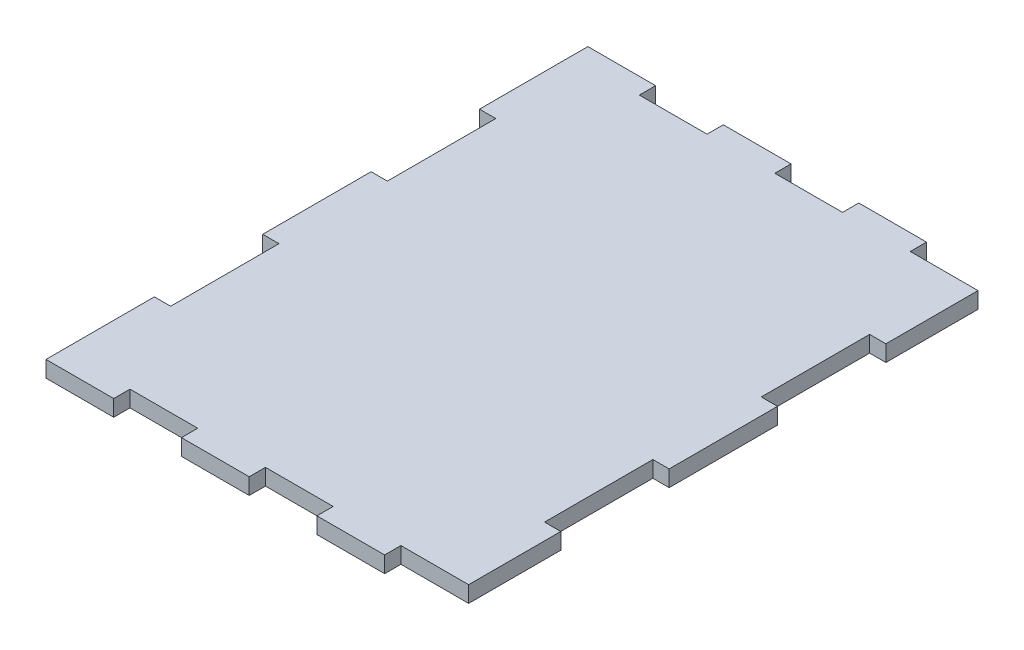
SolidWorks part; units mm, degrees
ref_plane "Front Plane" through (0, 0, 0) normal (0, 0, 1) x (1, 0, 0)
ref_plane "Top Plane" through (0, 0, 0) normal (0, 1, 0) x (1, 0, 0)
ref_plane "Right Plane" through (0, 0, 0) normal (1, 0, 0) x (0, 0, -1)
sketch "Sketch1" plane through (0, 0, 0) normal (0, 1, 0) x (1, 0, 0)
  line L1 (150, 0) -> (0, 0)
  line L2 (150, 0) -> (150, 200)
  line L3 (150, 200) -> (0, 200)
  line L4 (0, 0) -> (0, 200)
  point P4 (0, 0)
  dimension "D1" = 150
  dimension "D2" = 200
extrude "Boss-Extrude1" add sketch "Sketch1" along normal blind 6
sketch "Sketch2" plane through (0, 6, 0) normal (0, 1, 0) x (1, 0, 0)
  line L0 (0, 0) -> (150, 0) construction
  line L1 (25, 0) -> (50, 0)
  line L2 (25, 0) -> (25, 6)
  line L3 (25, 6) -> (50, 6)
  line L4 (50, 0) -> (50, 6)
  line L5 (0, 200) -> (0, 0) construction
  line L6 (75, 0) -> (75, 6)
  line L7 (75, 0) -> (100, 0)
  line L8 (100, 0) -> (100, 6)
  line L9 (75, 6) -> (100, 6)
  line L10 (125, 0) -> (125, 6)
  line L11 (125, 0) -> (150, 0)
  line L12 (150, 0) -> (150, 6)
  line L13 (125, 6) -> (150, 6)
  line L14 (25, 194) -> (25, 200)
  line L15 (25, 194) -> (50, 194)
  line L16 (50, 194) -> (50, 200)
  line L17 (25, 200) -> (50, 200)
  line L18 (75, 194) -> (75, 200)
  line L19 (75, 194) -> (100, 194)
  line L20 (100, 194) -> (100, 200)
  line L21 (75, 200) -> (100, 200)
  line L22 (125, 194) -> (125, 200)
  line L23 (125, 194) -> (150, 194)
  line L24 (150, 194) -> (150, 200)
  line L25 (125, 200) -> (150, 200)
  line L26 (150, 200) -> (0, 200) construction
  line L27 (0, 160) -> (6, 160)
  line L28 (0, 160) -> (0, 120)
  line L29 (0, 120) -> (6, 120)
  line L30 (6, 160) -> (6, 120)
  line L31 (144, 160) -> (144, 120)
  line L32 (144, 160) -> (150, 160)
  line L33 (150, 160) -> (150, 120)
  line L34 (144, 120) -> (150, 120)
  line L35 (144, 80) -> (144, 40)
  line L36 (144, 80) -> (150, 80)
  line L37 (150, 80) -> (150, 40)
  line L38 (144, 40) -> (150, 40)
  line L39 (0, 80) -> (0, 40)
  line L40 (0, 80) -> (6, 80)
  line L41 (6, 80) -> (6, 40)
  line L42 (0, 40) -> (6, 40)
  dimension "D1" = 25
  dimension "D2" = 25
  dimension "D3" = 6
  dimension "D6" = 40
  dimension "D7" = 40
  dimension "D8" = 6
  dimension "D4" = 3
  dimension "D5" = 2
  dimension "D9" = 2
  dimension "D10" = 2
extrude "Cut-Extrude1" cut sketch "Sketch2" against normal blind 6
